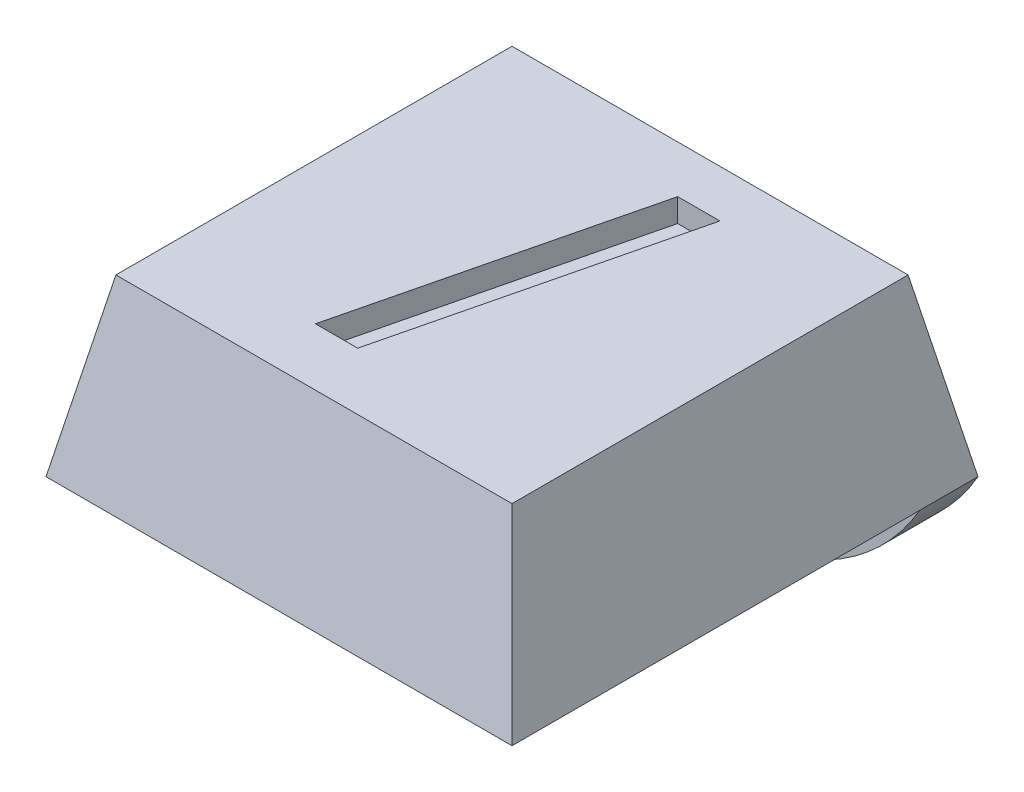
SolidWorks part; units mm, degrees
ref_plane "Front Plane" through (0, 0, 0) normal (0, 0, 1) x (1, 0, 0)
ref_plane "Top Plane" through (0, 0, 0) normal (0, 1, 0) x (1, 0, 0)
ref_plane "Right Plane" through (0, 0, 0) normal (1, 0, 0) x (0, 0, -1)
sketch "Sketch1" plane through (0, 0, 0) normal (0, 1, 0) x (1, 0, 0)
  line L1 (0, 0) -> (8, 0)
  line L2 (0, 0) -> (0, 8)
  line L3 (0, 8) -> (8, 8)
  line L4 (8, 0) -> (8, 8)
  dimension "D1" = 8
  dimension "D2" = 8
extrude "Boss-Extrude1" add sketch "Sketch1" along normal blind 3
sketch "Sketch2" plane through (0, 0, 0) normal (0, 0, 1) x (1, 0, 0)
  line L0 (0, 0) -> (0.6, 3)
  line L1 (0, 3) -> (8, 3) construction
  line L2 (0.6, 3) -> (0, 3)
  line L3 (0, 3) -> (0, 0)
  line L4 (8, 0) -> (7.4, 3)
  line L5 (7.4, 3) -> (8, 3)
  line L6 (8, 3) -> (8, 0)
  dimension "D1" = 0.6
  dimension "D2" = 0.6
extrude "Cut-Extrude1" cut sketch "Sketch2" against normal through all both and the other way through all
sketch "Sketch3" plane through (0, 0, 0) normal (1, 0, 0) x (0, 0, -1)
  line L0 (0, 0) -> (0.6, 3)
  line L1 (8, 3) -> (0, 3) construction
  line L2 (0.6, 3) -> (0, 3)
  line L3 (0, 3) -> (0, 0)
  line L4 (8, 3) -> (7.4, 3)
  line L5 (7.4, 3) -> (8, 0)
  line L6 (8, 3) -> (8, 0)
  dimension "D1" = 0.6
  dimension "D2" = 0.6
extrude "Cut-Extrude2" cut sketch "Sketch3" along normal blind 11
sketch "Sketch4" plane through (0, 0, 0) normal (0, -1, 0) x (1, 0, 0)
  line L0 (8, 0) -> (8, -8) construction
  line L3 (0, 0) -> (8, 0) construction
  circle A0 centre (4, -3.75) radius 1.8
  dimension "D1" = 3.6
  dimension "D2" = 4
  dimension "D3" = 3.75
extrude "Cut-Extrude3" cut sketch "Sketch4" against normal blind 0.8
sketch "Sketch5" plane through (0, 0, 0) normal (0, -1, 0) x (1, 0, 0)
  line L0 (8, 0) -> (8, -8) construction
  line L1 (0, -8) -> (8, -8)
  line L2 (0, -8) -> (0, -7)
  line L3 (0, -7) -> (8, -7)
  line L4 (8, -8) -> (8, -7)
  dimension "D1" = 1
extrude "Boss-Extrude2" add sketch "Sketch5" along normal blind 2
fillet "Fillet1" radius 4 2 edges at (8, -2, -7.5) (0, -2, -7.5)
sketch "Sketch6" plane through (0, 3, 0) normal (0, 1, 0) x (1, 0, 0)
  text T0 "/" font "Arial" height 5
extrude "Cut-Extrude4" cut sketch "Sketch6" against normal blind 0.4
